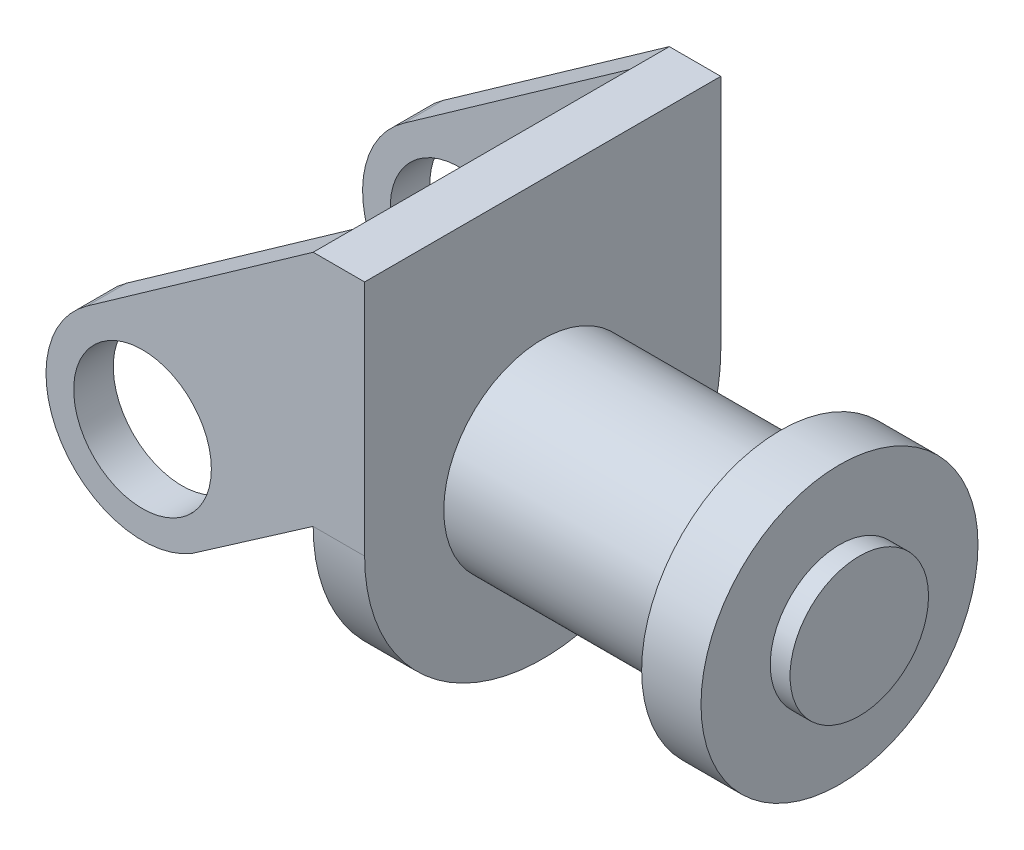
SolidWorks part; units mm, degrees
ref_plane "Front Plane" through (0, 0, 0) normal (0, 0, 1) x (1, 0, 0)
ref_plane "Top Plane" through (0, 0, 0) normal (0, 1, 0) x (1, 0, 0)
ref_plane "Right Plane" through (0, 0, 0) normal (1, 0, 0) x (0, 0, -1)
sketch "Sketch1" plane through (0, 0, 0) normal (1, 0, 0) x (0, 0, -1)
  line L1 (-0.045, 0) -> (0.045, 0)
  line L2 (-0.045, 0) -> (-0.045, -0.06)
  line L4 (0.045, 0) -> (0.045, -0.06)
  arc A0 (-0.045, -0.06) -> (0.045, -0.06) centre (0, -0.06) ccw
  point P5 (0, 0)
  dimension "D1" = 0.06
  dimension "D2" = 0.09
extrude "Boss-Extrude1" add sketch "Sketch1" along normal blind 0.013 contours L1 L4 A0 L2
ref_point "Point1"
sketch "Sketch2" plane through (0.013, 0, 0) normal (1, 0, 0) x (0, 0, -1)
  circle A0 centre (0, -0.06) radius 0.025
  arc A1 (-0.045, -0.06) -> (0.045, -0.06) centre (0, -0.06) ccw construction
  dimension "D1" = 0.05
extrude "Boss-Extrude2" add sketch "Sketch2" along normal blind 0.075
ref_plane "Plane1" through (0.073, 0, 0) normal (1, 0, 0) x (0, 0, -1)
sketch "Sketch3" plane through (0.073, 0, 0) normal (1, 0, 0) x (0, 0, -1)
  circle A0 centre (0, -0.06) radius 0.025 construction
  circle A1 centre (0, -0.06) radius 0.025
  circle A2 centre (0, -0.06) radius 0.035
  dimension "D1" = 0.01
extrude "Boss-Extrude3" add sketch "Sketch3" along normal up to surface (0.015 mm away) up to face at (0.088, -0.06, -0.025)
sketch "Sketch4" plane through (0.088, 0, 0) normal (1, 0, 0) x (0, 0, -1)
  circle A0 centre (0, -0.06) radius 0.0175
  dimension "D1" = 0.035
extrude "Boss-Extrude4" add sketch "Sketch4" along normal blind 0.005
sketch "Sketch5" plane through (0, 0, -0.045) normal (0, 0, -1) x (-1, 0, 0)
  line L0 (0, 0) -> (0.0572, -0.0404)
  line L1 (0, -0.06) -> (0.0307, -0.0813)
  line L9 (0, -0.06) -> (0, 0)
  line L10 (0, 0) -> (-0.013, 0)
  line L11 (-0.013, 0) -> (-0.013, -0.06)
  line L12 (-0.013, -0.06) -> (0, -0.06)
  line L14 (0, 0) -> (-0.013, 0)
  line L15 (-0.013, 0) -> (-0.013, -0.06)
  line L16 (-0.013, -0.06) -> (0, -0.06)
  arc A1 (0.0572, -0.0404) -> (0.0307, -0.0813) centre (0.0431, -0.0603) cw
  dimension "D1" = 0
  dimension "D2" = 0.07
ref_axis "Axis1" through (0.013, 0, -0.045) along (-1, 0, 0)
extrude "Boss-Extrude5" add sketch "Sketch5" against normal blind 0.01
mirror "Mirror1" about plane through (0, 0, 0) normal (0, 0, 1) of "Boss-Extrude5"
sketch "Sketch6" plane through (0, 0, 0.045) normal (0, 0, 1) x (1, 0, 0)
  line L0 (-0.0636, -0.0735) -> (-0.0577, -0.0697) construction
  circle A0 centre (-0.0431, -0.0603) radius 0.0174
  arc A1 (-0.0572, -0.0404) -> (-0.0307, -0.0813) centre (-0.0431, -0.0603) ccw construction
  point P8 (0, 0)
  point P9 (-0.057, -0.0693)
  dimension "D1" = 0.007
extrude "Cut-Extrude1" cut sketch "Sketch6" against normal through all
